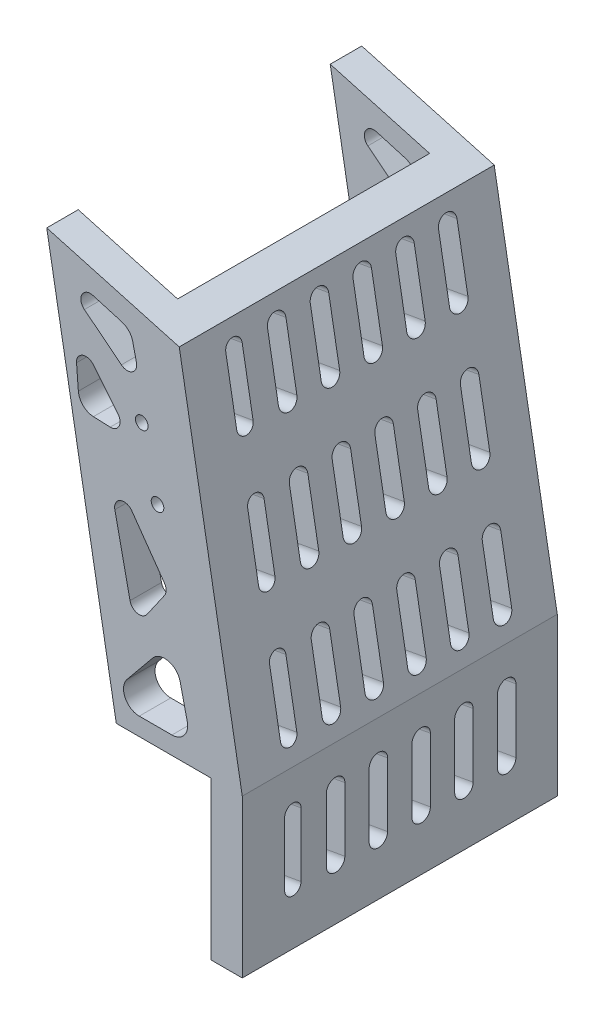
SolidWorks part; units mm, degrees
ref_plane "Front Plane" through (0, 0, 0) normal (0, 0, 1) x (1, 0, 0)
ref_plane "Top Plane" through (0, 0, 0) normal (0, 1, 0) x (1, 0, 0)
ref_plane "Right Plane" through (0, 0, 0) normal (1, 0, 0) x (0, 0, -1)
sketch "Sketch1" plane through (0, 0, 0) normal (0, 0, 1) x (1, 0, 0)
  line L0 (0, 0) -> (-25, 0)
  line L1 (-25, 0) -> (-79.4657, 79.8008)
  line L2 (-54.687, 126.7128) -> (122.9469, 126.7128)
  line L3 (122.9469, 126.7128) -> (130, 86.7128)
  line L4 (130, 86.7128) -> (-16.8223, 86.7128)
  line L5 (-25.0818, 71.0755) -> (0, 34.3267)
  line L6 (0, 34.3267) -> (0, 0)
  line L7 (0, 30) -> (150, 30) construction
  line L8 (150, 30) -> (150, -13.554) construction
  line L9 (140, 14.2228) -> (140, 30) construction
  line L10 (140, 30) -> (116.1596, 165.2058) construction
  line L17 (87.6026, 114.9555) -> (115.4893, 101.0273)
  line L18 (114.1489, 95.3435) -> (67.8789, 95.3435)
  line L19 (66.0673, 100.7346) -> (84.4504, 114.6628)
  line L20 (-0.4911, 115.0579) -> (27.4755, 101.0248)
  line L21 (26.1301, 95.3435) -> (-20.1398, 95.3435)
  line L22 (-21.9652, 100.7242) -> (-3.6619, 114.7573)
  line L26 (26.031, 117.4787) -> (61.4709, 117.4787)
  line L27 (63.2826, 112.0875) -> (49.1628, 101.3896)
  line L28 (46.0057, 101.0994) -> (24.6856, 111.7973)
  line L29 (-44.3201, 47.3006) -> (-34.0482, 32.2506)
  line L30 (-30.0093, 31.3799) -> (-16.8655, 39.389)
  line L31 (-17.5627, 44.8238) -> (-40.9784, 51.8647)
  arc A0 (-79.4657, 79.8008) -> (-54.687, 126.7128) centre (-54.687, 96.7128) cw
  arc A1 (-16.8223, 86.7128) -> (-25.0818, 71.0755) centre (-16.8223, 76.7128) ccw
  circle A2 centre (-54.687, 96.7128) radius 9.5
  arc A9 (115.4893, 101.0273) -> (114.1489, 95.3435) centre (114.1489, 98.3435) cw
  arc A10 (67.8789, 95.3435) -> (66.0673, 100.7346) centre (67.8789, 98.3435) cw
  arc A11 (87.6026, 114.9555) -> (84.4504, 114.6628) centre (86.2621, 112.2716) ccw
  arc A12 (27.4755, 101.0248) -> (26.1301, 95.3435) centre (26.1301, 98.3435) cw
  arc A13 (-20.1398, 95.3435) -> (-21.9652, 100.7242) centre (-20.1398, 98.3435) cw
  arc A14 (-0.4911, 115.0579) -> (-3.6619, 114.7573) centre (-1.8366, 112.3765) ccw
  arc A18 (49.1628, 101.3896) -> (46.0057, 101.0994) centre (47.3511, 103.7808) cw
  arc A19 (61.4709, 117.4787) -> (63.2826, 112.0875) centre (61.4709, 114.4787) cw
  arc A20 (26.031, 117.4787) -> (24.6856, 111.7973) centre (26.031, 114.4787) ccw
  arc A21 (-34.0482, 32.2506) -> (-30.0093, 31.3799) centre (-31.5703, 33.9418) ccw
  arc A22 (-16.8655, 39.389) -> (-17.5627, 44.8238) centre (-18.4265, 41.9508) ccw
  arc A23 (-44.3201, 47.3006) -> (-40.9784, 51.8647) centre (-41.8423, 48.9918) cw
  circle A24 centre (118.0922, 116.7128) radius 2
  circle A25 centre (123.0922, 96.7128) radius 2
  dimension "D10" = 30
  dimension "D11" = 10
  dimension "D12" = 19
  dimension "D13" = 3
  dimension "D14" = 3
  dimension "D15" = 4
  dimension "D16" = 4
  dimension "D2" = 40
  dimension "D3" = 40
  dimension "D4" = 30
  dimension "D5" = 25
  dimension "D6" = 150
  dimension "D7" = 10
  dimension "D8" = 130
  dimension "D9" = 80
  dimension "D17" = 10
  dimension "D18" = 10
  dimension "D19" = 5
sketch "Sketch3" plane through (0, 0, 0) normal (0, 0, 1) x (1, 0, 0)
  line L0 (140, 30) -> (116.1596, 165.2058) construction
  line L1 (119.4711, 146.4251) -> (140, 30)
  line L2 (0, 30) -> (150, 30) construction
  line L3 (140, 30) -> (140, -20)
  line L4 (150, 30) -> (150, -20)
  line L6 (0, 30) -> (150, 30)
  line L8 (87.9244, 155.197) -> (129.9867, 143.5011)
  line L9 (129.9867, 143.5011) -> (150, 30)
  line L10 (140, -20) -> (150, -20)
  line L11 (140, -20) -> (110, -20)
  line L12 (110, -20) -> (110, 30)
  line L13 (110, 30) -> (87.9244, 155.197)
  line L14 (102.5933, 143.9536) -> (111.7468, 141.2839)
  line L15 (115.2199, 137.6033) -> (116.4135, 132.4076)
  line L16 (111.6218, 129.3883) -> (99.8855, 138.726)
  line L17 (102.7031, 124.9705) -> (110.5205, 115.3764)
  line L18 (108.0701, 110.4839) -> (102.7378, 110.7058)
  line L19 (97.9601, 115.3212) -> (97.3861, 122.8473)
  line L23 (114.9332, 90.9011) -> (125.2782, 76.2524)
  line L24 (130.2675, 51.6601) -> (132.5401, 41.7676)
  line L25 (127.667, 35.6482) -> (117.2995, 35.6482)
  line L26 (113.4299, 43.8146) -> (121.5249, 53.7071)
  line L27 (121.5771, 22.3858) -> (135.7065, 10.8237)
  line L28 (130.8654, 2.2429) -> (116.736, 7.2655)
  line L29 (113.4106, 11.9767) -> (113.4106, 18.5162)
  line L30 (125.2927, 72.8119) -> (119.7645, 64.8427)
  line L31 (114.3653, 65.9278) -> (109.5485, 88.5457)
  circle A0 centre (123.0922, 96.7128) radius 2 construction
  circle A1 centre (118.0922, 116.7128) radius 2 construction
  circle A2 centre (123.0922, 96.7128) radius 2
  circle A3 centre (118.0922, 116.7128) radius 2
  arc A4 (135.7065, 10.8237) -> (130.8654, 2.2429) centre (132.5401, 6.9541) cw
  arc A5 (116.736, 7.2655) -> (113.4106, 11.9767) centre (118.4106, 11.9767) cw
  arc A6 (121.5771, 22.3858) -> (113.4106, 18.5162) centre (118.4106, 18.5162) ccw
  arc A7 (132.5401, 41.7676) -> (127.667, 35.6482) centre (127.667, 40.6482) cw
  arc A8 (117.2995, 35.6482) -> (113.4299, 43.8146) centre (117.2995, 40.6482) cw
  arc A9 (121.5249, 53.7071) -> (130.2675, 51.6601) centre (125.3944, 50.5406) cw
  arc A13 (102.7378, 110.7058) -> (97.9601, 115.3212) centre (102.9456, 115.7014) cw
  arc A14 (111.7468, 141.2839) -> (115.2199, 137.6033) centre (110.3468, 136.4839) cw
  arc A15 (102.7031, 124.9705) -> (97.3861, 122.8473) centre (100.3774, 123.0755) ccw
  arc A16 (110.5205, 115.3764) -> (108.0701, 110.4839) centre (108.1948, 113.4813) cw
  arc A17 (116.4135, 132.4076) -> (111.6218, 129.3883) centre (113.4896, 131.736) cw
  arc A18 (102.5933, 143.9536) -> (99.8855, 138.726) centre (101.7533, 141.0736) ccw
  arc A19 (125.2782, 76.2524) -> (125.2927, 72.8119) centre (122.8277, 74.5218) cw
  arc A20 (119.7645, 64.8427) -> (114.3653, 65.9278) centre (117.2995, 66.5527) cw
  arc A21 (114.9332, 90.9011) -> (109.5485, 88.5457) centre (112.4827, 89.1705) ccw
  dimension "D3" = 5
  dimension "D4" = 3
  dimension "D5" = 3
  dimension "D1" = 50
  dimension "D2" = 40
extrude "Boss-Extrude4" add sketch "Sketch3" along normal mid plane 100 contours L13 L6 L1 L8 A3 A2 | L9 L8 L1 L6 | L12 L11 L3 L6 | L3 L10 L4 L6 region at (134.8427, 87.4846, 0) region at (113.7418, 92.4855, 0) region at (145, 5, 0) region at (125.2097, 3.0631, 0)
extrude "Cut-Extrude4" cut sketch "Sketch3<5>" against normal mid plane 80 contours L13 L6 L1 L8 A3 A2 | L12 L11 L3 L6 region at (113.7418, 92.4855, 0) region at (125.2097, 3.0631, 0)
sketch "Sketch3<5>" plane through (0, 0, 0) normal (0, 0, 1) x (1, 0, 0) same geometry as "Sketch3"
sketch "Sketch4" plane through (150.6072, 26.5561, 0) normal (0.9848, 0.1736, 0) x (0, 0, -1)
  line L0 (-33.9402, 111.1274) -> (-33.9402, 91.1837) construction
  line L7 (50, 105.2377) -> (50, 91.1837) construction
  line L8 (-31.3406, 111.1274) -> (-31.3406, 91.1837)
  line L9 (-36.5397, 111.1274) -> (-36.5397, 91.1837)
  line L10 (-20.3641, 111.1274) -> (-20.3641, 91.1837) construction
  line L11 (-17.4396, 111.1274) -> (-17.4396, 91.1837)
  line L12 (-23.2886, 111.1274) -> (-23.2886, 91.1837)
  line L13 (-6.788, 111.1274) -> (-6.788, 91.1837) construction
  line L14 (-3.8635, 111.1274) -> (-3.8635, 91.1837)
  line L15 (-9.7125, 111.1274) -> (-9.7125, 91.1837)
  line L16 (6.788, 111.1274) -> (6.788, 91.1837) construction
  line L17 (9.7125, 111.1274) -> (9.7125, 91.1837)
  line L18 (3.8635, 111.1274) -> (3.8635, 91.1837)
  line L19 (20.3641, 111.1274) -> (20.3641, 91.1837) construction
  line L20 (23.2886, 111.1274) -> (23.2886, 91.1837)
  line L21 (17.4396, 111.1274) -> (17.4396, 91.1837)
  line L22 (33.9402, 111.1274) -> (33.9402, 91.1837) construction
  line L23 (36.8647, 111.1274) -> (36.8647, 91.1837)
  line L24 (31.0157, 111.1274) -> (31.0157, 91.1837)
  line L25 (-33.9402, 101.1556) -> (-20.3641, 101.1556) construction
  line L26 (-20.3641, 101.1556) -> (-6.788, 101.1556) construction
  line L27 (-6.788, 101.1556) -> (6.788, 101.1556) construction
  line L28 (6.788, 101.1556) -> (20.3641, 101.1556) construction
  line L29 (20.3641, 101.1556) -> (33.9402, 101.1556) construction
  line L30 (-36.5397, 71.1274) -> (-36.5397, 51.1837)
  line L31 (0, 114.2398) -> (0, 95.2398) construction
  line L32 (0, 97.0004) -> (0, 117.1439) construction
  line L33 (0, 134.7398) -> (0, 92.3876) construction
  line L34 (-31.3406, 71.1274) -> (-31.3406, 51.1837)
  line L35 (-23.2886, 71.1274) -> (-23.2886, 51.1837)
  line L36 (-17.4396, 71.1274) -> (-17.4396, 51.1837)
  line L37 (-3.8635, 71.1274) -> (-3.8635, 51.1837)
  line L38 (-9.7125, 71.1274) -> (-9.7125, 51.1837)
  line L39 (9.7125, 71.1274) -> (9.7125, 51.1837)
  line L40 (3.8635, 71.1274) -> (3.8635, 51.1837)
  line L41 (23.2886, 71.1274) -> (23.2886, 51.1837)
  line L42 (17.4396, 71.1274) -> (17.4396, 51.1837)
  line L43 (36.8647, 71.1274) -> (36.8647, 51.1837)
  line L44 (31.0157, 71.1274) -> (31.0157, 51.1837)
  line L45 (-33.9402, 71.1274) -> (-33.9402, 51.1837) construction
  line L46 (-20.3641, 71.1274) -> (-20.3641, 51.1837) construction
  line L47 (-6.788, 71.1274) -> (-6.788, 51.1837) construction
  line L48 (6.788, 71.1274) -> (6.788, 51.1837) construction
  line L49 (20.3641, 71.1274) -> (20.3641, 51.1837) construction
  line L50 (33.9402, 71.1274) -> (33.9402, 51.1837) construction
  line L51 (-36.5397, 31.1274) -> (-36.5397, 11.1837)
  line L52 (-31.3406, 31.1274) -> (-31.3406, 11.1837)
  line L53 (-23.2886, 31.1274) -> (-23.2886, 11.1837)
  line L54 (-17.4396, 31.1274) -> (-17.4396, 11.1837)
  line L55 (-3.8635, 31.1274) -> (-3.8635, 11.1837)
  line L56 (-9.7125, 31.1274) -> (-9.7125, 11.1837)
  line L57 (9.7125, 31.1274) -> (9.7125, 11.1837)
  line L58 (3.8635, 31.1274) -> (3.8635, 11.1837)
  line L59 (23.2886, 31.1274) -> (23.2886, 11.1837)
  line L60 (17.4396, 31.1274) -> (17.4396, 11.1837)
  line L61 (36.8647, 31.1274) -> (36.8647, 11.1837)
  line L62 (31.0157, 31.1274) -> (31.0157, 11.1837)
  line L63 (-33.9402, 31.1274) -> (-33.9402, 11.1837) construction
  line L64 (-20.3641, 31.1274) -> (-20.3641, 11.1837) construction
  line L65 (-6.788, 31.1274) -> (-6.788, 11.1837) construction
  line L66 (6.788, 31.1274) -> (6.788, 11.1837) construction
  line L67 (20.3641, 31.1274) -> (20.3641, 11.1837) construction
  line L68 (33.9402, 31.1274) -> (33.9402, 11.1837) construction
  line L69 (-36.5397, -8.8726) -> (-36.5397, -28.8163)
  line L70 (-31.3406, -8.8726) -> (-31.3406, -28.8163)
  line L71 (-23.2886, -8.8726) -> (-23.2886, -28.8163)
  line L72 (-17.4396, -8.8726) -> (-17.4396, -28.8163)
  line L73 (-3.8635, -8.8726) -> (-3.8635, -28.8163)
  line L74 (-9.7125, -8.8726) -> (-9.7125, -28.8163)
  line L75 (9.7125, -8.8726) -> (9.7125, -28.8163)
  line L76 (3.8635, -8.8726) -> (3.8635, -28.8163)
  line L77 (23.2886, -8.8726) -> (23.2886, -28.8163)
  line L78 (17.4396, -8.8726) -> (17.4396, -28.8163)
  line L79 (36.8647, -8.8726) -> (36.8647, -28.8163)
  line L80 (31.0157, -8.8726) -> (31.0157, -28.8163)
  line L81 (-33.9402, -8.8726) -> (-33.9402, -28.8163) construction
  line L82 (-20.3641, -8.8726) -> (-20.3641, -28.8163) construction
  line L83 (-6.788, -8.8726) -> (-6.788, -28.8163) construction
  line L84 (6.788, -8.8726) -> (6.788, -28.8163) construction
  line L85 (20.3641, -8.8726) -> (20.3641, -28.8163) construction
  line L86 (33.9402, -8.8726) -> (33.9402, -28.8163) construction
  line L87 (-36.5397, 111.1274) -> (-36.5397, 71.1274) construction
  arc A0 (-31.3406, 111.1274) -> (-36.5397, 111.1274) centre (-33.9402, 111.1274) ccw
  arc A1 (-36.5397, 91.1837) -> (-31.3406, 91.1837) centre (-33.9402, 91.1837) ccw
  arc A2 (-17.4396, 111.1274) -> (-23.2886, 111.1274) centre (-20.3641, 111.1274) ccw
  arc A3 (-23.2886, 91.1837) -> (-17.4396, 91.1837) centre (-20.3641, 91.1837) ccw
  arc A4 (-3.8635, 111.1274) -> (-9.7125, 111.1274) centre (-6.788, 111.1274) ccw
  arc A5 (-9.7125, 91.1837) -> (-3.8635, 91.1837) centre (-6.788, 91.1837) ccw
  arc A6 (9.7125, 111.1274) -> (3.8635, 111.1274) centre (6.788, 111.1274) ccw
  arc A7 (3.8635, 91.1837) -> (9.7125, 91.1837) centre (6.788, 91.1837) ccw
  arc A8 (23.2886, 111.1274) -> (17.4396, 111.1274) centre (20.3641, 111.1274) ccw
  arc A9 (17.4396, 91.1837) -> (23.2886, 91.1837) centre (20.3641, 91.1837) ccw
  arc A10 (36.8647, 111.1274) -> (31.0157, 111.1274) centre (33.9402, 111.1274) ccw
  arc A11 (31.0157, 91.1837) -> (36.8647, 91.1837) centre (33.9402, 91.1837) ccw
  arc A12 (-31.3406, 71.1274) -> (-36.5397, 71.1274) centre (-33.9402, 71.1274) ccw
  arc A13 (-36.5397, 51.1837) -> (-31.3406, 51.1837) centre (-33.9402, 51.1837) ccw
  arc A14 (-17.4396, 71.1274) -> (-23.2886, 71.1274) centre (-20.3641, 71.1274) ccw
  arc A15 (-23.2886, 51.1837) -> (-17.4396, 51.1837) centre (-20.3641, 51.1837) ccw
  arc A16 (-9.7125, 51.1837) -> (-3.8635, 51.1837) centre (-6.788, 51.1837) ccw
  arc A17 (-3.8635, 71.1274) -> (-9.7125, 71.1274) centre (-6.788, 71.1274) ccw
  arc A18 (3.8635, 51.1837) -> (9.7125, 51.1837) centre (6.788, 51.1837) ccw
  arc A19 (9.7125, 71.1274) -> (3.8635, 71.1274) centre (6.788, 71.1274) ccw
  arc A20 (17.4396, 51.1837) -> (23.2886, 51.1837) centre (20.3641, 51.1837) ccw
  arc A21 (23.2886, 71.1274) -> (17.4396, 71.1274) centre (20.3641, 71.1274) ccw
  arc A22 (31.0157, 51.1837) -> (36.8647, 51.1837) centre (33.9402, 51.1837) ccw
  arc A23 (36.8647, 71.1274) -> (31.0157, 71.1274) centre (33.9402, 71.1274) ccw
  arc A24 (-31.3406, 31.1274) -> (-36.5397, 31.1274) centre (-33.9402, 31.1274) ccw
  arc A25 (-36.5397, 11.1837) -> (-31.3406, 11.1837) centre (-33.9402, 11.1837) ccw
  arc A26 (-17.4396, 31.1274) -> (-23.2886, 31.1274) centre (-20.3641, 31.1274) ccw
  arc A27 (-23.2886, 11.1837) -> (-17.4396, 11.1837) centre (-20.3641, 11.1837) ccw
  arc A28 (-9.7125, 11.1837) -> (-3.8635, 11.1837) centre (-6.788, 11.1837) ccw
  arc A29 (-3.8635, 31.1274) -> (-9.7125, 31.1274) centre (-6.788, 31.1274) ccw
  arc A30 (3.8635, 11.1837) -> (9.7125, 11.1837) centre (6.788, 11.1837) ccw
  arc A31 (9.7125, 31.1274) -> (3.8635, 31.1274) centre (6.788, 31.1274) ccw
  arc A32 (17.4396, 11.1837) -> (23.2886, 11.1837) centre (20.3641, 11.1837) ccw
  arc A33 (23.2886, 31.1274) -> (17.4396, 31.1274) centre (20.3641, 31.1274) ccw
  arc A34 (31.0157, 11.1837) -> (36.8647, 11.1837) centre (33.9402, 11.1837) ccw
  arc A35 (36.8647, 31.1274) -> (31.0157, 31.1274) centre (33.9402, 31.1274) ccw
  arc A36 (-31.3406, -8.8726) -> (-36.5397, -8.8726) centre (-33.9402, -8.8726) ccw
  arc A37 (-36.5397, -28.8163) -> (-31.3406, -28.8163) centre (-33.9402, -28.8163) ccw
  arc A38 (-17.4396, -8.8726) -> (-23.2886, -8.8726) centre (-20.3641, -8.8726) ccw
  arc A39 (-23.2886, -28.8163) -> (-17.4396, -28.8163) centre (-20.3641, -28.8163) ccw
  arc A40 (-9.7125, -28.8163) -> (-3.8635, -28.8163) centre (-6.788, -28.8163) ccw
  arc A41 (-3.8635, -8.8726) -> (-9.7125, -8.8726) centre (-6.788, -8.8726) ccw
  arc A42 (3.8635, -28.8163) -> (9.7125, -28.8163) centre (6.788, -28.8163) ccw
  arc A43 (9.7125, -8.8726) -> (3.8635, -8.8726) centre (6.788, -8.8726) ccw
  arc A44 (17.4396, -28.8163) -> (23.2886, -28.8163) centre (20.3641, -28.8163) ccw
  arc A45 (23.2886, -8.8726) -> (17.4396, -8.8726) centre (20.3641, -8.8726) ccw
  arc A46 (31.0157, -28.8163) -> (36.8647, -28.8163) centre (33.9402, -28.8163) ccw
  arc A47 (36.8647, -8.8726) -> (31.0157, -8.8726) centre (33.9402, -8.8726) ccw
  point P2 (-33.9402, 101.1556)
  point P7 (-20.3641, 101.1556)
  point P19 (-6.788, 101.1556)
  point P26 (6.788, 101.1556)
  point P33 (20.3641, 101.1556)
  point P40 (33.9402, 101.1556)
  point P63 (-33.9402, 61.1556)
  point P68 (-20.3641, 61.1556)
  point P75 (-6.788, 61.1556)
  point P82 (6.788, 61.1556)
  point P89 (20.3641, 61.1556)
  point P96 (33.9402, 61.1556)
  point P105 (-33.9402, 21.1556)
  point P110 (-20.3641, 21.1556)
  point P117 (-6.788, 21.1556)
  point P124 (6.788, 21.1556)
  point P131 (20.3641, 21.1556)
  point P138 (33.9402, 21.1556)
  point P147 (-33.9402, -18.8444)
  point P152 (-20.3641, -18.8444)
  point P159 (-6.788, -18.8444)
  point P166 (6.788, -18.8444)
  point P173 (20.3641, -18.8444)
  point P180 (33.9402, -18.8444)
  dimension "D1" = 40
extrude "Cut-Extrude5" cut sketch "Sketch4" against normal mid plane 80
sketch "Sketch5" plane through (140, 0, 0) normal (-1, 0, 0) x (0, 0, 1)
  line L1 (63.2549, 30.0036) -> (-82.5895, 30.0036)
  line L2 (63.2549, 30.0036) -> (63.2549, -22.5099)
  line L3 (63.2549, -22.5099) -> (-82.5895, -22.5099)
  line L4 (-82.5895, 30.0036) -> (-82.5895, -22.5099)
extrude "Cut-Extrude6" cut sketch "Sketch5" along normal through all
